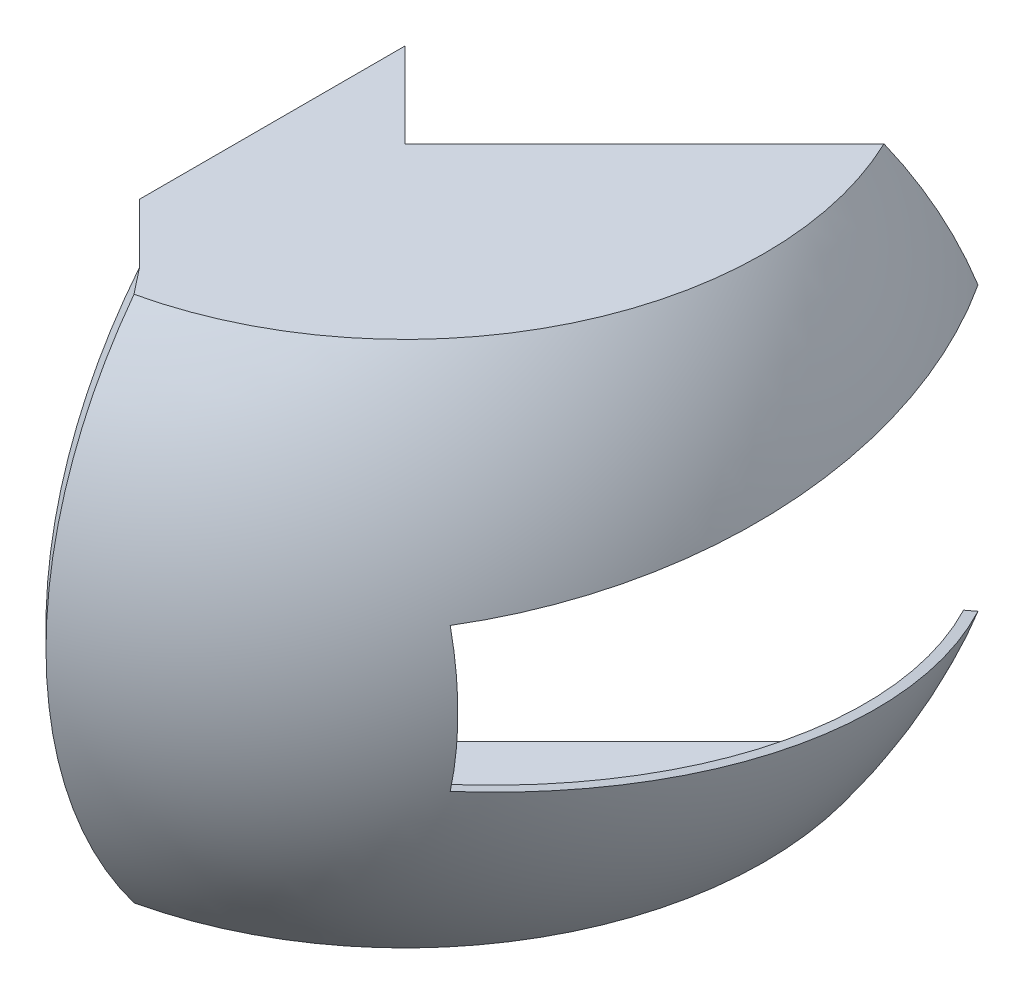
SolidWorks part; units mm, degrees
ref_plane "Front Plane" through (0, 0, 0) normal (0, 0, 1) x (1, 0, 0)
ref_plane "Top Plane" through (0, 0, 0) normal (0, 1, 0) x (1, 0, 0)
ref_plane "Right Plane" through (0, 0, 0) normal (1, 0, 0) x (0, 0, -1)
sketch "Sketch1" plane through (0, 0, 0) normal (1, 0, 0) x (0, 0, -1)
  line L0 (0, 0) -> (-58.4615, 0) construction
  line L1 (0, -55) -> (0, 55)
  line L2 (0, 55) -> (-75, 55)
  line L3 (0, -55) -> (-75, -55)
  arc A0 (-75, 55) -> (-75, -55) centre (0, 0) ccw
  dimension "D1" = 55
  dimension "D2" = 75
revolve "Revolve1" add sketch "Sketch1" angle 180 about L1
sketch "Sketch2" plane through (0, -55, 0) normal (0, -1, 0) x (1, 0, 0)
  line L0 (0, 0) -> (0, 40)
  line L1 (0, 75) -> (0, -75) construction
  line L2 (0, 40) -> (12.2873, 48.6036)
  line L3 (12.2873, 48.6036) -> (12.2873, 112.2596)
  line L4 (0, 0) -> (17.6777, 17.6777)
  line L5 (17.6777, 17.6777) -> (97.0571, -61.7018)
  line L6 (12.2873, 112.2596) -> (-94.5819, 112.2596)
  line L7 (-94.5819, 112.2596) -> (-94.5819, -108.4776)
  line L8 (-94.5819, -108.4776) -> (97.0571, -108.4776)
  line L9 (97.0571, -108.4776) -> (97.0571, -61.7018)
  dimension "D1" = 40
  dimension "D2" = 15
  dimension "D3" = 125
  dimension "D4" = 25
  dimension "D5" = 45
extrude "Cut-Extrude1" cut sketch "Sketch2" against normal through all
ref_plane "Plane1" through (100, 0, 0) normal (1, 0, 0) x (0, 0, -1)
sketch "Sketch3" plane through (100, 0, 0) normal (1, 0, 0) x (0, 0, -1)
  line L0 (0, 0) -> (-60, 0) construction
  line L1 (-60, -15) -> (-60, 15)
  line L2 (0, 0) -> (45.6666, 0) construction
  line L3 (45.6666, -30) -> (45.6666, 30)
  line L4 (45.6666, 30) -> (-60, 15)
  line L5 (45.6666, -30) -> (-60, -15)
  ellipse E0 centre (-17.6777, 0) end of major axis (-17.6777, 89.5824) minor radius 63.3443 (32.3223, -55) -> (32.3223, 55) ccw construction
  dimension "D1" = 60
  dimension "D2" = 15
  dimension "D3" = 30
extrude "Cut-Extrude2" cut sketch "Sketch3" against normal through all
chamfer "Chamfer1" distance 5 angle 45 1 edges at (12.2873, 0, 92.1901)
shell "Shell1" thickness 2
sketch "Sketch4" plane through (0, -55, 0) normal (0, -1, 0) x (1, 0, 0)
  line L0 (12.2873, 67.6544) -> (0, 55.3671)
  line L1 (12.2873, 48.6036) -> (12.2873, 67.6544) construction
  line L2 (0, 40) -> (0, 55.3671)
  line L3 (0, 40) -> (12.2873, 48.6036)
  line L4 (12.2873, 48.6036) -> (12.2873, 67.6544)
  dimension "D1" = 45
extrude "Boss-Extrude1" add sketch "Sketch4" against normal blind 2
ref_plane "Plane2" through (0, 0, 0) normal (0, 1, 0) x (1, 0, 0)
mirror "Mirror1" about plane through (0, 0, 0) normal (0, 1, 0) of "Boss-Extrude1"
